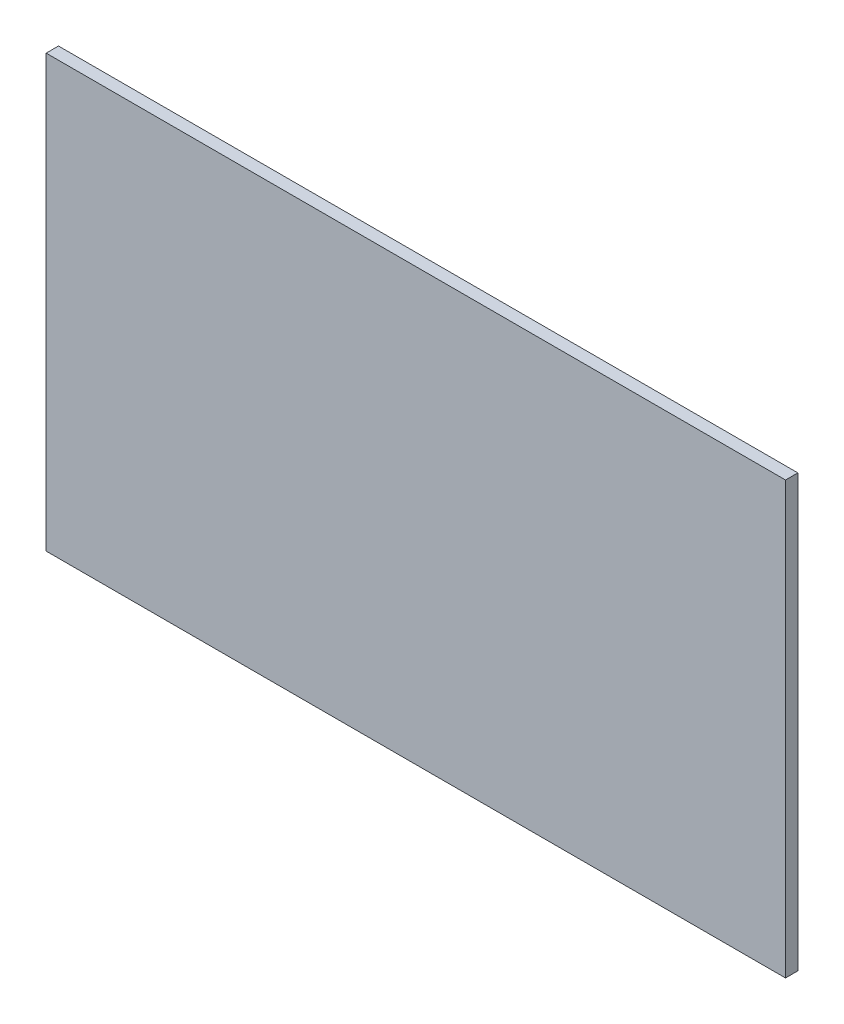
SolidWorks part; units mm, degrees
ref_plane "前视基准面" through (0, 0, 0) normal (0, 0, 1) x (1, 0, 0)
ref_plane "上视基准面" through (0, 0, 0) normal (0, 1, 0) x (1, 0, 0)
ref_plane "右视基准面" through (0, 0, 0) normal (1, 0, 0) x (0, 0, -1)
sketch "草图1" plane through (0, 0, 0) normal (0, 0, 1) x (1, 0, 0)
  line L1 (-90, 52.5) -> (90, 52.5)
  line L2 (-90, 52.5) -> (-90, -52.5)
  line L3 (-90, -52.5) -> (90, -52.5)
  line L4 (90, 52.5) -> (90, -52.5)
  line L5 (-90, 52.5) -> (90, -52.5) construction
  line L6 (-90, -52.5) -> (90, 52.5) construction
  point P0 (0, 0)
  dimension "D1" = 105
  dimension "D2" = 180
extrude "凸台-拉伸1" add sketch "草图1" along normal blind 3
